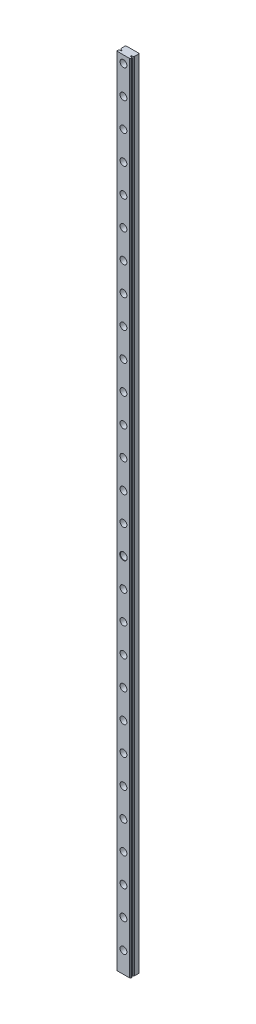
SolidWorks part; units mm, degrees
material "Alloy Steel (SS)"
ref_plane "Horní rovina" through (0, 0, 0) normal (0, 0, 1) x (1, 0, 0)
ref_plane "Přední rovina" through (0, 0, 0) normal (0, 1, 0) x (1, 0, 0)
ref_plane "Pravá rovina" through (0, 0, 0) normal (1, 0, 0) x (0, 0, -1)
sketch "Skica1" plane through (0, 0, 0) normal (0, 1, 0) x (1, 0, 0)
  line L0 (-5.5, -8) -> (5.5, -8)
  line L2 (6, -7.5) -> (6, -6.6619)
  line L3 (5.2091, -6) -> (4, -5.95)
  line L4 (4, -5.95) -> (4, -5.05)
  line L5 (4, -5.05) -> (5.2091, -5)
  line L6 (6, -4.3381) -> (6, -0.5)
  line L8 (5.5, 0) -> (-1.6, 0)
  line L9 (-2.4, 0) -> (-5.5, 0)
  line L11 (-6, -0.5) -> (-6, -4.3381)
  line L12 (-5.2091, -5) -> (-4, -5.05)
  line L13 (-4, -5.05) -> (-4, -5.95)
  line L14 (-4, -5.95) -> (-5.2091, -6)
  line L15 (-6, -6.6619) -> (-6, -7.5)
  line L17 (0, -9.4784) -> (0, 1.3023) construction
  line L18 (5.5, -8) -> (6, -7.5)
  line L19 (-6, -7.5) -> (-5.5, -8)
  line L20 (-5.5, 0) -> (-6, -0.5)
  line L21 (6, -0.5) -> (5.5, 0)
  line L22 (4, -5.5) -> (-4, -5.5) construction
  arc A0 (5.2091, -6) -> (6, -6.6619) centre (6.3, -5.5) ccw
  arc A1 (6, -4.3381) -> (5.2091, -5) centre (6.3, -5.5) ccw
  arc A2 (-2.4, 0) -> (-1.6, 0) centre (-2, 0.3) ccw
  arc A5 (-6, -4.3381) -> (-5.2091, -5) centre (-6.3, -5.5) cw
  arc A6 (-5.2091, -6) -> (-6, -6.6619) centre (-6.3, -5.5) cw
  point P0 (-6, -8)
  point P1 (6, -8)
  point P14 (6, 0)
  point P19 (-6, 0)
  dimension "D4" = 1.2
  dimension "D18" = 0.5
  dimension "D1" = 6
  dimension "D3" = 8
  dimension "D5" = 6.3
  dimension "D6" = 5.5
  dimension "D7" = 4
  dimension "D8" = 4
  dimension "D13" = 0.9
  dimension "D14" = 0.9
  dimension "D15" = 5.5
  dimension "D16" = 1
  dimension "D17" = 0.5
  dimension "D19" = 2
  dimension "D20" = 0.3
  dimension "D9" = 0.5
  dimension "D10" = 0.5
  dimension "D11" = 0.5
  dimension "D12" = 0.5
  dimension "D21" = 0.5
  dimension "D22" = 0.5
  dimension "D23" = 0.5
  dimension "D24" = 0.5
  dimension "D25" = 6
extrude "Delka" add sketch "Skica1" along normal blind 362.75
sketch "Sketch1" plane through (0, 0, 0) normal (0, -1, 0) x (1, 0, 0)
  line L17 (6, 6.6619) -> (6, 7.5)
  line L18 (6, 7.5) -> (5.5, 8)
  line L19 (5.5, 8) -> (-5.5, 8)
  line L20 (-5.5, 8) -> (-6, 7.5)
  line L21 (-6, 7.5) -> (-6, 6.6619)
  line L22 (-5.2091, 6) -> (-4, 5.95)
  line L23 (-4, 5.95) -> (-4, 5.05)
  line L24 (-4, 5.05) -> (-5.2091, 5)
  line L25 (-6, 4.3381) -> (-6, 0.5)
  line L26 (-6, 0.5) -> (-5.5, 0)
  line L27 (-5.5, 0) -> (-2.4, 0)
  line L28 (-1.6, 0) -> (5.5, 0)
  line L29 (5.5, 0) -> (6, 0.5)
  line L30 (6, 0.5) -> (6, 4.3381)
  line L31 (5.2091, 5) -> (4, 5.05)
  line L32 (4, 5.05) -> (4, 5.95)
  line L33 (4, 5.95) -> (5.2091, 6)
  line L34 (6, 6.6619) -> (6, 7.5)
  line L35 (6, 7.5) -> (5.5, 8)
  line L36 (5.5, 8) -> (-5.5, 8)
  line L37 (-5.5, 8) -> (-6, 7.5)
  line L38 (-6, 7.5) -> (-6, 6.6619)
  line L39 (-5.2091, 6) -> (-4, 5.95)
  line L40 (-4, 5.95) -> (-4, 5.05)
  line L41 (-4, 5.05) -> (-5.2091, 5)
  line L42 (-6, 4.3381) -> (-6, 0.5)
  line L43 (-6, 0.5) -> (-5.5, 0)
  line L44 (-5.5, 0) -> (-2.4, 0)
  line L45 (-1.6, 0) -> (5.5, 0)
  line L46 (5.5, 0) -> (6, 0.5)
  line L47 (6, 0.5) -> (6, 4.3381)
  line L48 (5.2091, 5) -> (4, 5.05)
  line L49 (4, 5.05) -> (4, 5.95)
  line L50 (4, 5.95) -> (5.2091, 6)
  arc A5 (6, 6.6619) -> (5.2091, 6) centre (6.3, 5.5) ccw
  arc A6 (-5.2091, 6) -> (-6, 6.6619) centre (-6.3, 5.5) ccw
  arc A7 (-6, 4.3381) -> (-5.2091, 5) centre (-6.3, 5.5) ccw
  arc A8 (-1.6, 0) -> (-2.4, 0) centre (-2, -0.3) ccw
  arc A9 (5.2091, 5) -> (6, 4.3381) centre (6.3, 5.5) ccw
  arc A10 (6, 6.6619) -> (5.2091, 6) centre (6.3, 5.5) ccw
  arc A11 (-5.2091, 6) -> (-6, 6.6619) centre (-6.3, 5.5) ccw
  arc A12 (-6, 4.3381) -> (-5.2091, 5) centre (-6.3, 5.5) ccw
  arc A13 (-1.6, 0) -> (-2.4, 0) centre (-2, -0.3) ccw
  arc A14 (5.2091, 5) -> (6, 4.3381) centre (6.3, 5.5) ccw
  dimension "D1" = 0
extrude "Boss-Extrude1" add sketch "Sketch1" along normal blind 337.25
hole_wizard "Díra1" positions "Skica3" profile "Skica4" legacy end condition through all
sketch "Skica3" plane through (0, 0, 8) normal (0, 0, 1) x (1, 0, 0)
  point P0 (0, -18.875)
  point P2 (0, -18.875)
  dimension "D1" = 18.875
sketch "Skica4" plane through (0, -18.875, 8) normal (1, 0, 0) x (0, -1, 0)
  line L0 (0, 0) -> (0, 8)
  line L1 (0, 8) -> (1.75, 8)
  line L2 (1.75, 8) -> (1.75, 4.5)
  line L3 (1.75, 4.5) -> (3, 4.5)
  line L4 (3, 4.5) -> (3, 0)
  line L5 (3, 0) -> (0, 0)
  line L6 (0, 110) -> (0, -10) construction
  dimension "Průměr" = 3.5
  dimension "Hloubka" = 8
  dimension "Průměr válc. zahloubení" = 6
  dimension "Hloubka válc. zahloubení" = 4.5
chamfer "Zkosení1" distance 0.3 angle 45 2 edges at (1.75, -18.875, 0) (3, -18.875, 8)
pattern_linear "LPattern1" count 13 spacing 25 along (0, -1, 0) count 16 spacing 25 along (0, 1, 0) of "Díra1" pattern seed only yes
equation "\"D17@Skica1\"=\"D16@Skica1\"/2"
equation "\"D10@Skica1\"=\"D9@Skica1\""
equation "\"D11@Skica1\"=\"D9@Skica1\""
equation "\"D12@Skica1\"=\"D9@Skica1\""
equation "\"D21@Skica1\"=\"D9@Skica1\""
equation "\"D22@Skica1\"=\"D9@Skica1\""
equation "\"D23@Skica1\"=\"D9@Skica1\""
equation "\"D24@Skica1\"=\"D9@Skica1\""
equation "\"P\"= 25mm"
equation "\"Emin\"= 5mm"
equation "\"Emax\"= 20mm"
equation "\"Hc\"= round (  ( \"D1@Delka\" - 2 * \"Emin\" )  / \"P\" ) "
equation "\"E\"= ( \"L\" - ( ( \"Hc\" - 1 ) * \"P\" ) ) / 2"
equation "\"L\"=362.75"
equation "\"D1@Delka\" = \"L\""
equation "\"D1\"= \"Hc\""
equation "\"D3\"= \"P\""
equation "\"D1@Skica3\"= \"E\""
equation "\"D25@Skica1\"=\"D1@Skica1\""
equation "\"Přidat vysunutím1\"= \"L\""
equation "\"Delka\"= \"L\""
